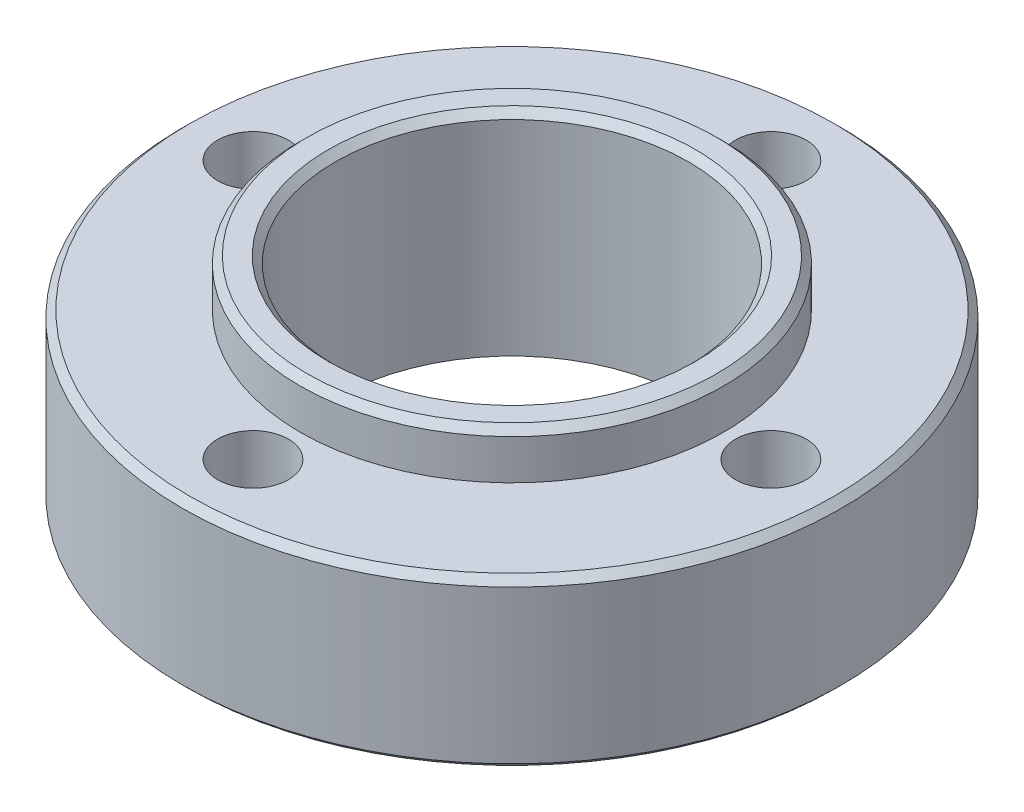
SolidWorks part; units mm, degrees
ref_plane "Спереди" through (0, 0, 0) normal (0, 0, 1) x (1, 0, 0)
ref_plane "Сверху" through (0, 0, 0) normal (0, 1, 0) x (1, 0, 0)
ref_plane "Справа" through (0, 0, 0) normal (1, 0, 0) x (0, 0, -1)
sketch "Эскиз1" plane through (0, 0, 0) normal (0, 1, 0) x (1, 0, 0)
  circle A0 centre (0, 0) radius 14
  circle A1 centre (0, 0) radius 9
  circle A2 centre (0, 0) radius 11 construction
  circle A3 centre (0, 11) radius 1.5
  circle A4 centre (11, 0) radius 1.5
  circle A5 centre (0, -11) radius 1.5
  circle A6 centre (-11, 0) radius 1.5
  circle A7 centre (0, 0) radius 7.5
  point P16 (0, 0)
  dimension "D1" = 18
  dimension "D2" = 28
  dimension "D3" = 22
  dimension "D4" = 4
extrude "Бобышка-Вытянуть1" add sketch "Эскиз1" along normal blind 7 contours A0 A6 A5 A4 A3 A1 | A1 A7 region at (-13.604, 0, 0) region at (-8.7454, 0, 0)
extrude "Бобышка-Вытянуть2" add sketch "Эскиз1<3>" along normal blind 9 contours A1 A7 region at (-8.7454, 0, 0)
sketch "Эскиз1<3>" plane through (0, 0, 0) normal (0, 1, 0) x (1, 0, 0) same geometry as "Эскиз1"
chamfer "Фаска1" distance 0.3 angle 45 3 edges at (0, 9, 9) (0, 7, 14) (0, 9, 7.5)
chamfer "Фаска4" distance 0.2 angle 45 1 edges at (0, 0, 14)
